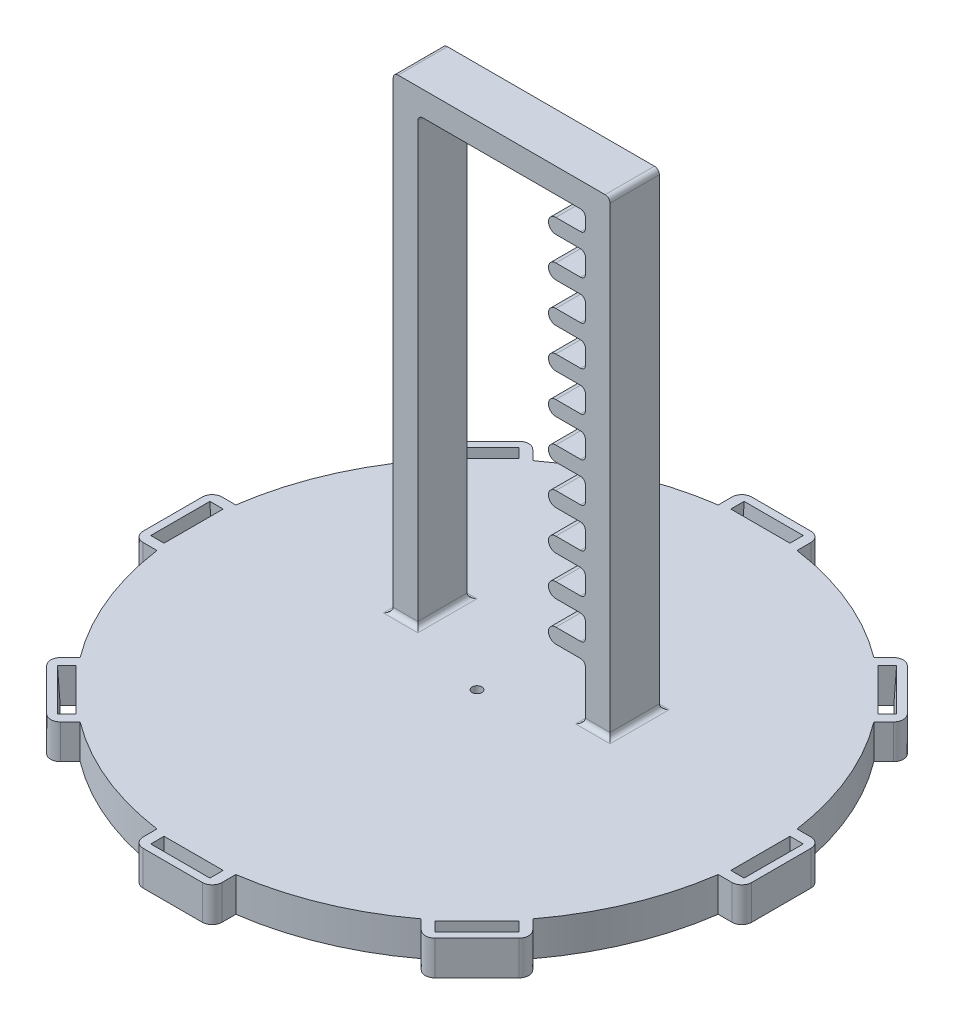
SolidWorks part; units mm, degrees
ref_plane "Front Plane" through (0, 0, 0) normal (0, 0, 1) x (1, 0, 0)
ref_plane "Top Plane" through (0, 0, 0) normal (0, 1, 0) x (1, 0, 0)
ref_plane "Right Plane" through (0, 0, 0) normal (1, 0, 0) x (0, 0, -1)
sketch "Sketch1" plane through (0, 0, 0) normal (0, 1, 0) x (1, 0, 0)
  line L0 (-8, 56.9408) -> (-8, 59.7408)
  line L1 (0, 57.5) -> (0, -57.5) construction
  line L2 (8, 56.9408) -> (8, 59.7408)
  line L3 (-6, 61.7408) -> (6, 61.7408)
  line L4 (39.4147, 47.8999) -> (47.8999, 39.4147)
  line L9 (34.6063, 45.9201) -> (36.5862, 47.8999)
  line L10 (45.9201, 34.6063) -> (47.8999, 36.5862)
  line L15 (61.7408, 6) -> (61.7408, -6)
  line L16 (56.9408, 8) -> (59.7408, 8)
  line L17 (56.9408, -8) -> (59.7408, -8)
  line L22 (47.8999, -39.4147) -> (39.4147, -47.8999)
  line L23 (45.9201, -34.6063) -> (47.8999, -36.5862)
  line L24 (34.6063, -45.9201) -> (36.5862, -47.8999)
  line L29 (6, -61.7408) -> (-6, -61.7408)
  line L30 (8, -56.9408) -> (8, -59.7408)
  line L31 (-8, -56.9408) -> (-8, -59.7408)
  line L36 (-39.4147, -47.8999) -> (-47.8999, -39.4147)
  line L37 (-34.6063, -45.9201) -> (-36.5862, -47.8999)
  line L38 (-45.9201, -34.6063) -> (-47.8999, -36.5862)
  line L43 (-61.7408, -6) -> (-61.7408, 6)
  line L44 (-56.9408, -8) -> (-59.7408, -8)
  line L45 (-56.9408, 8) -> (-59.7408, 8)
  line L50 (-47.8999, 39.4147) -> (-39.4147, 47.8999)
  line L51 (-45.9201, 34.6063) -> (-47.8999, 36.5862)
  line L52 (-34.6063, 45.9201) -> (-36.5862, 47.8999)
  arc A0 (-8, 56.9408) -> (-34.6063, 45.9201) centre (0, 0) ccw
  arc A1 (6, 61.7408) -> (8, 59.7408) centre (6, 59.7408) cw
  arc A2 (-6, 61.7408) -> (-8, 59.7408) centre (-6, 59.7408) ccw
  arc A3 (39.4147, 47.8999) -> (36.5862, 47.8999) centre (38.0005, 46.4857) ccw
  arc A4 (47.8999, 39.4147) -> (47.8999, 36.5862) centre (46.4857, 38.0005) cw
  arc A5 (61.7408, 6) -> (59.7408, 8) centre (59.7408, 6) ccw
  arc A6 (61.7408, -6) -> (59.7408, -8) centre (59.7408, -6) cw
  arc A7 (47.8999, -39.4147) -> (47.8999, -36.5862) centre (46.4857, -38.0005) ccw
  arc A8 (39.4147, -47.8999) -> (36.5862, -47.8999) centre (38.0005, -46.4857) cw
  arc A9 (6, -61.7408) -> (8, -59.7408) centre (6, -59.7408) ccw
  arc A10 (-6, -61.7408) -> (-8, -59.7408) centre (-6, -59.7408) cw
  arc A11 (-39.4147, -47.8999) -> (-36.5862, -47.8999) centre (-38.0005, -46.4857) ccw
  arc A12 (-47.8999, -39.4147) -> (-47.8999, -36.5862) centre (-46.4857, -38.0005) cw
  arc A13 (-61.7408, -6) -> (-59.7408, -8) centre (-59.7408, -6) ccw
  arc A14 (-61.7408, 6) -> (-59.7408, 8) centre (-59.7408, 6) cw
  arc A15 (-47.8999, 39.4147) -> (-47.8999, 36.5862) centre (-46.4857, 38.0005) ccw
  arc A16 (-39.4147, 47.8999) -> (-36.5862, 47.8999) centre (-38.0005, 46.4857) cw
  arc A17 (-45.9201, 34.6063) -> (-56.9408, 8) centre (0, 0) ccw
  arc A18 (-56.9408, -8) -> (-45.9201, -34.6063) centre (0, 0) ccw
  arc A19 (34.6063, 45.9201) -> (8, 56.9408) centre (0, 0) ccw
  arc A20 (-34.6063, -45.9201) -> (-8, -56.9408) centre (0, 0) ccw
  arc A21 (8, -56.9408) -> (34.6063, -45.9201) centre (0, 0) ccw
  arc A22 (45.9201, -34.6063) -> (56.9408, -8) centre (0, 0) ccw
  arc A23 (56.9408, 8) -> (45.9201, 34.6063) centre (0, 0) ccw
  point P11 (8, 61.7408)
  point P14 (-8, 61.7408)
  point P17 (-8, 58.3408)
  point P98 (0, 0)
  dimension "D1" = 115
  dimension "D2" = 2
  dimension "D3" = 16
  dimension "D4" = 2.8
  dimension "D7" = 8
extrude "Boss-Extrude1" add sketch "Sketch1" along normal blind 7
sketch "Sketch2" plane through (0, 7, 0) normal (0, 1, 0) x (1, 0, 0)
  line L0 (-57.5, 0) -> (57.5, 0) construction
  line L1 (0, 0) -> (0, 10) construction
  line L7 (17, 5) -> (22, 5)
  line L14 (0, 10) -> (29.7122, 10) construction
  line L15 (0, 10) -> (-19.5, 10) construction
  line L17 (17, 5) -> (17, 15)
  line L18 (-22, 15) -> (-17, 15)
  line L19 (-22, 15) -> (-22, 5)
  line L20 (-22, 5) -> (-17, 5)
  line L21 (-17, 15) -> (-17, 5)
  line L22 (-22, 15) -> (-17, 5) construction
  line L23 (-22, 5) -> (-17, 15) construction
  line L24 (17, 15) -> (22, 15)
  line L25 (22, 5) -> (22, 15)
  line L26 (17, 5) -> (22, 15) construction
  line L27 (17, 15) -> (22, 5) construction
  circle A0 centre (0, 0) radius 57.5 construction
  point P8 (19.5, 10)
  dimension "D1" = 10
  dimension "D2" = 17
  dimension "D3" = 17
  dimension "D4" = 10
  dimension "D5" = 5
  dimension "D6" = 10
  dimension "D7" = 5
extrude "Boss-Extrude2" add sketch "Sketch2" along normal blind 95
sketch "Sketch15" plane through (0, 0, 0) normal (0, -1, 0) x (1, 0, 0)
  circle A0 centre (0, 0) radius 1
  dimension "D1" = 2
extrude "Cut-Extrude3" cut sketch "Sketch15" along direction (0, 1, 0) on the side against the normal up to surface (7 mm away) contours A0 up to face at (0, 7, 0)
sketch "Sketch16" plane through (0, 0, 0) normal (0, -1, 0) x (1, 0, 0)
  line L1 (-6, 59.8) -> (6, 59.8)
  line L2 (-6, 59.8) -> (-6, 57.5)
  line L3 (-6, 57.5) -> (6, 57.5)
  line L4 (6, 59.8) -> (6, 57.5)
  point P5 (0, 57.5)
  dimension "D1" = 2.3
  dimension "D2" = 12
  dimension "D3" = 57.5
sketch "Sketch17" plane through (0, 7, 0) normal (0, 1, 0) x (1, 0, 0)
  line L0 (-6, -57.5) -> (6, -57.5) construction
  line L1 (-6, -57.5) -> (6, -57.5)
  line L2 (-6, -57.5) -> (-6, -60.2)
  line L3 (-6, -60.2) -> (6, -60.2)
  line L4 (6, -60.2) -> (6, -57.5)
  dimension "D1" = 2.7
ref_axis "Axis1" through (0, 107.1, 0) along (0, -1, 0)
loft "Cut-Loft2" cut profiles "Sketch16", "Sketch17" connector at (6, 0, 59.8) connector at (6, 7, 60.2)
pattern_circular "CirPattern1" count 8 over 360 about axis through (0, 107.1, 0) along (0, -1, 0) of "Cut-Loft2"
sketch "Sketch18" plane through (-17, 0, 0) normal (1, 0, 0) x (0, 0, -1)
  line L0 (15, 102) -> (15, 7) construction
  line L1 (5, 102) -> (15, 102)
  line L2 (5, 102) -> (5, 97)
  line L3 (5, 97) -> (15, 97)
  line L4 (15, 102) -> (15, 97)
  dimension "D1" = 5
extrude "Boss-Extrude3" add sketch "Sketch18" along normal up to surface (34 mm away) up to face at (17, 54.5, -10)
sketch "Sketch19" plane through (0, 0, -15) normal (0, 0, -1) x (-1, 0, 0)
  line L0 (-17, 93) -> (-11, 93)
  line L1 (-17, 97) -> (-17, 7) construction
  line L4 (-11, 91.5) -> (-19.8185, 91.5) construction
  line L5 (-17, 90) -> (-11, 90)
  line L6 (-17, 93) -> (-17, 90)
  arc A1 (-11, 93) -> (-11, 90) centre (-11, 91.5) cw
  dimension "D1" = 6
  dimension "D4" = 3
  dimension "D3" = 4
extrude "Boss-Extrude4" add sketch "Sketch19" against normal blind 10
fillet "Fillet1" radius 1 2 edges at (17, 93, -10) (17, 90, -10)
fillet "Fillet2" radius 1 12 edges at (-22, 102, -10) (22, 102, -10) (17, 7, -10) (19.5, 7, -15) (19.5, 7, -5) (22, 7, -10) (-19.5, 7, -5) (-19.5, 7, -15) (-22, 7, -10) (-17, 7, -10) (-17, 97, -10) (17, 97, -10)
pattern_linear "LPattern2" count 10 spacing 8 along (0, -1, 0) of "Fillet1", "Boss-Extrude4"
equation "\"85.00.00mm\"=8500"
